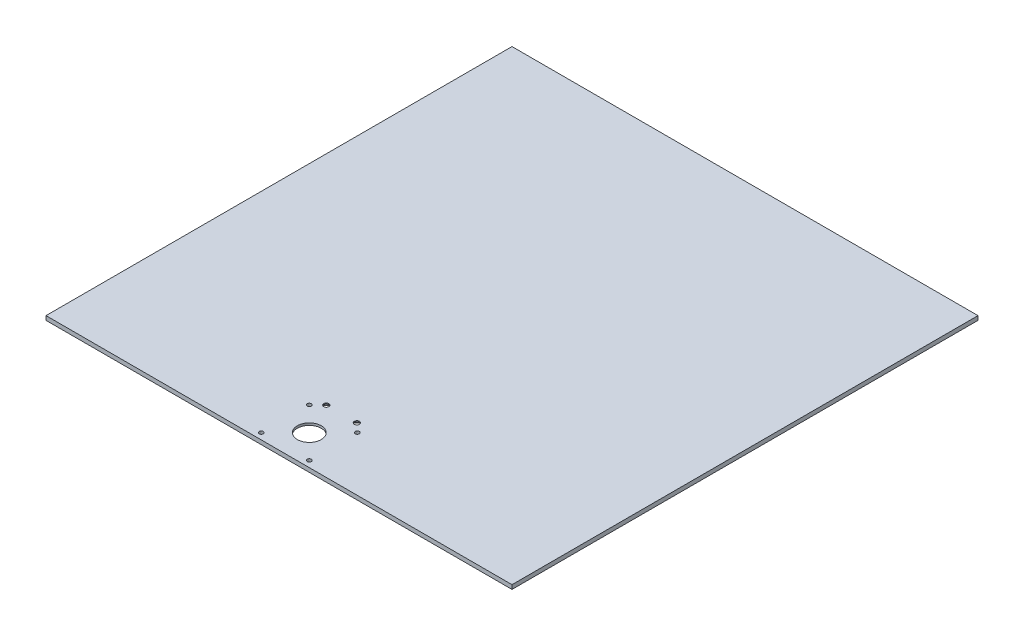
SolidWorks part; units mm, degrees
material "6061-T6 (SS)"
ref_plane "Front Plane" through (0, 0, 0) normal (0, 0, 1) x (1, 0, 0)
ref_plane "Top Plane" through (0, 0, 0) normal (0, 1, 0) x (1, 0, 0)
ref_plane "Right Plane" through (0, 0, 0) normal (1, 0, 0) x (0, 0, -1)
sketch "Sketch1" plane through (0, 0, 0) normal (0, 1, 0) x (1, 0, 0)
  line L1 (-228.6, -228.6) -> (228.6, -228.6)
  line L2 (-228.6, -228.6) -> (-228.6, 228.6)
  line L3 (-228.6, 228.6) -> (228.6, 228.6)
  line L4 (228.6, -228.6) -> (228.6, 228.6)
  line L5 (-228.6, -228.6) -> (228.6, 228.6) construction
  line L6 (-228.6, 228.6) -> (228.6, -228.6) construction
  point P0 (0, 0)
  dimension "D1" = 457.2
  dimension "D2" = 457.2
extrude "Boss-Extrude1" add sketch "Sketch1" along normal blind 4.064
sketch "Sketch2" plane through (0, 0, 0) normal (0, -1, 0) x (1, 0, 0)
  line L0 (0, -55) -> (0, 55) construction
  line L1 (-228.6, 228.6) -> (228.6, 228.6) construction
  circle A0 centre (0, 198.882) radius 19.177
  point P2 (0, 0)
  point P5 (0, 0)
  point P6 (0, 0)
  dimension "D1" = 38.354
  dimension "D2" = 29.718
extrude "Cut-Extrude1" cut sketch "Sketch2" against normal blind 1.905
sketch "Sketch3" plane through (0, 1.905, 0) normal (0, -1, 0) x (1, 0, 0)
  circle A0 centre (0, 198.882) radius 11.7475
  circle A1 centre (0, 198.882) radius 19.177 construction
  point P2 (0, 0)
  dimension "D1" = 23.495
extrude "Cut-Extrude2" cut sketch "Sketch3" against normal up to next
hole_wizard "#10-32 Tapped Hole1" positions "Sketch7" profile "Sketch8" tap size "#10-32" standard "ANSI Inch" end condition through all
sketch "Sketch7" plane through (0, 0, 0) normal (0, -1, 0) x (-1, 0, 0.0002)
  point P0 (23.6171, -222.4505)
  point P1 (-23.5293, -222.4598)
sketch "Sketch8" plane through (-23.5732, 0, 222.4552) normal (1, 0, 0) x (0, 0, -1)
  line L0 (0, 0) -> (0, 4.064)
  line L1 (0, 4.064) -> (2.0193, 4.064)
  line L2 (2.0193, 4.064) -> (2.0193, 0)
  line L3 (2.0193, 0) -> (0, 0)
  line L4 (0, -6.35) -> (0, 107.95) construction
  dimension "Thru Tap Drill Dia." = 4.0386
  dimension "Thru Tap Drill Depth" = 4.064
cosmetic thread "Hole Thread1" parameters "D1"=4.7625, "D2"=4.826
cosmetic thread "Hole Thread2" parameters "D1"=4.7625, "D2"=4.826
hole_wizard "#10-32 Tapped Hole2" positions "Sketch9" profile "Sketch10" tap size "#10-32" standard "ANSI Inch" end condition through all
sketch "Sketch9" plane through (0, 0, 0) normal (0, -1, 0) x (-1, 0, 0.0002)
  point P0 (23.6078, -175.3042)
  point P1 (-23.5386, -175.3135)
  point P4 (0, 0)
sketch "Sketch10" plane through (-23.5732, 0, 175.3088) normal (1, 0, 0) x (0, 0, -1)
  line L0 (0, 0) -> (0, 4.064)
  line L1 (0, 4.064) -> (2.0193, 4.064)
  line L2 (2.0193, 4.064) -> (2.0193, 0)
  line L3 (2.0193, 0) -> (0, 0)
  line L4 (0, -6.35) -> (0, 107.95) construction
  dimension "Thru Tap Drill Dia." = 4.0386
  dimension "Thru Tap Drill Depth" = 4.064
cosmetic thread "Hole Thread3" parameters "D1"=4.7625, "D2"=4.826
cosmetic thread "Hole Thread4" parameters "D1"=4.7625, "D2"=4.826
hole_wizard "CBORE for #10 Binding Head Machine Screw1" positions "Sketch11" profile "Sketch12" counterbore size "#10" standard "ANSI Inch" end condition through all
sketch "Sketch11" plane through (0, 0, 0) normal (0, -1, 0) x (1, 0, 0)
  point P0 (-15, 167.1745)
  point P1 (15, 167.1745)
sketch "Sketch12" plane through (-15, 0, 167.1745) normal (1, 0, 0) x (0, 0, -1)
  line L0 (0, 0) -> (0, 4.064)
  line L1 (0, 4.064) -> (2.5527, 4.064)
  line L2 (2.5527, 4.064) -> (2.5527, 3.1242)
  line L3 (2.5527, 3.1242) -> (5.5562, 3.1242)
  line L4 (5.5562, 3.1242) -> (5.5562, 0)
  line L5 (5.5562, 0) -> (0, 0)
  line L6 (0, -6.35) -> (0, 107.95) construction
  dimension "Thru Hole Dia." = 5.1054
  dimension "Thru Hole Depth" = 4.064
  dimension "C'Bore Dia." = 11.1125
  dimension "C'Bore Depth" = 3.1242
